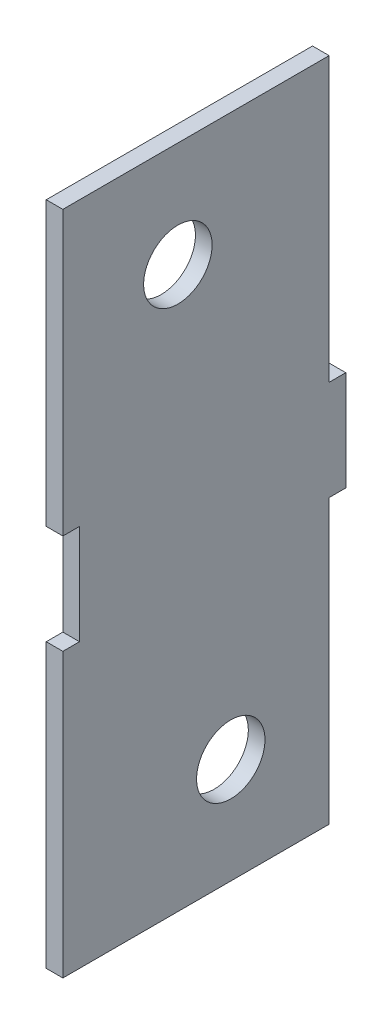
SolidWorks part; units mm, degrees
material "AISI 4130 Steel, annealed at 865C"
ref_plane "Front Plane" through (0, 0, 0) normal (0, 0, 1) x (1, 0, 0)
ref_plane "Top Plane" through (0, 0, 0) normal (0, 1, 0) x (1, 0, 0)
ref_plane "Right Plane" through (0, 0, 0) normal (1, 0, 0) x (0, 0, -1)
sketch "Sketch2" plane through (0, 0, 0) normal (1, 0, 0) x (0, 0, -1)
  line L0 (-1.7294, 21.6978) -> (3.3169, -21.6978) construction
  line L1 (-12.7, -31.75) -> (12.7, -31.75)
  line L2 (-12.7, -31.75) -> (-12.7, 31.75)
  line L3 (-12.7, 31.75) -> (12.7, 31.75)
  line L4 (12.7, -31.75) -> (12.7, 31.75)
  line L5 (-12.7, -31.75) -> (12.7, 31.75) construction
  line L6 (-12.7, 31.75) -> (12.7, -31.75) construction
  line L7 (0, 0) -> (0.7938, 0) construction
  circle A0 centre (-1.7294, 21.6978) radius 3.2639
  circle A1 centre (3.3169, -21.6978) radius 3.2639
  point P0 (0, 0)
  point P6 (0, 0)
  point P13 (0.7937, 0)
  dimension "D3" = 6.5278
  dimension "D4" = 6.5278
  dimension "D1" = 25.4
  dimension "D2" = 63.5
  dimension "D5" = 96.633
  dimension "D6" = 43.688
  dimension "D7" = 0.7937
extrude "Boss-Extrude1" add sketch "Sketch2" along normal blind 1.5875
sketch "Sketch3" plane through (1.5875, 0, 0) normal (1, 0, 0) x (0, 0, -1)
  line L0 (-12.7, 0) -> (12.7, 0) construction
  line L1 (-12.7, 31.75) -> (-12.7, -31.75) construction
  line L2 (12.7, -31.75) -> (12.7, 31.75) construction
  line L4 (-12.7, 4.7625) -> (-11.1125, 4.7625)
  line L5 (-12.7, 4.7625) -> (-12.7, -4.7625)
  line L6 (-12.7, -4.7625) -> (-11.1125, -4.7625)
  line L7 (-11.1125, 4.7625) -> (-11.1125, -4.7625)
  line L8 (12.7, 4.7625) -> (14.2875, 4.7625)
  line L9 (12.7, 4.7625) -> (12.7, -4.7625)
  line L10 (12.7, -4.7625) -> (14.2875, -4.7625)
  line L11 (14.2875, 4.7625) -> (14.2875, -4.7625)
  point P14 (-11.1125, 0)
  dimension "D1" = 9.525
  dimension "D2" = 1.5875
  dimension "D3" = 1.5875
extrude "Boss-Extrude2" add sketch "Sketch3" against normal blind 1.5875 contours L9 L8 L11 L10
extrude "Cut-Extrude1" cut sketch "Sketch3<4>" against normal blind 3.175 contours L7 L6 L5 L4
sketch "Sketch3<4>" plane through (1.5875, 0, 0) normal (1, 0, 0) x (0, 0, -1) same geometry as "Sketch3"
